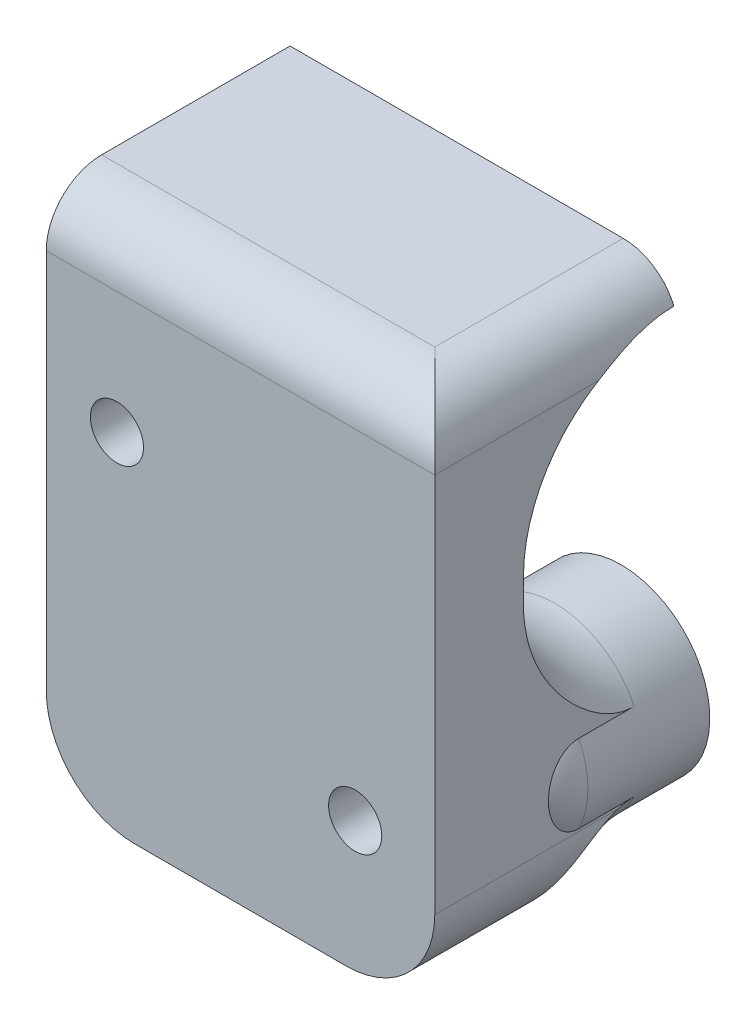
SolidWorks part; units mm, degrees
ref_plane "Front" through (0, 0, 0) normal (0, 0, 1) x (1, 0, 0)
ref_plane "Top" through (0, 0, 0) normal (0, 1, 0) x (1, 0, 0)
ref_plane "Right" through (0, 0, 0) normal (1, 0, 0) x (0, 0, -1)
sketch "Эскиз1" plane through (0, 0, 0) normal (0, 0, 1) x (1, 0, 0)
  line L0 (2.2009, 1.2487) -> (19.7294, 1.2487)
  line L1 (2.2009, 1.2487) -> (2.2009, 24.9297)
  line L2 (2.2009, 24.9297) -> (19.7294, 24.9297)
  line L3 (19.7294, 1.2487) -> (19.7294, 24.9297)
  circle A0 centre (16.1394, 7.1297) radius 1.2
  circle A1 centre (5.3909, 16.9297) radius 1.1977
  dimension "D1" = 3.19
  dimension "D2" = 17.5285
  dimension "D3" = 3.59
extrude "Бобышка-Вытянуть1" add sketch "Эскиз1" along normal blind 4
sketch "Эскиз2" plane through (0, 0, 0) normal (0, 0, -1) x (-1, 0, 0)
  line L0 (-2.2009, 24.9297) -> (-2.2009, 1.2487) construction
  line L1 (-19.7294, 24.9297) -> (-2.2009, 24.9297)
  line L2 (-19.7294, 24.9297) -> (-19.7294, 23.4297)
  line L3 (-19.7294, 23.4297) -> (-2.2009, 23.4297)
  line L4 (-2.2009, 24.9297) -> (-2.2009, 23.4297)
  dimension "D1" = 1.5
extrude "Бобышка-Вытянуть2" add sketch "Эскиз2" along normal blind 7
fillet "Скругление1" radius 4 2 edges at (2.2009, 1.2487, 2) (19.7294, 1.2487, 2)
sketch "Эскиз3" plane through (0, 0, 0) normal (0, 0, -1) x (-1, 0, 0)
  circle A0 centre (-16.1394, 7.1297) radius 1.1977
  circle A1 centre (-16.1394, 7.1297) radius 4
extrude "Бобышка-Вытянуть3" add sketch "Эскиз3" along normal blind 8
fillet "Скругление2" radius 5 1 edges at (12.1394, 7.1297, 0)
fillet "Скругление3" radius 7 1 edges at (10.9651, 23.4297, 0)
fillet "Скругление4" radius 2.5 1 edges at (20.1394, 7.1297, 0)
fillet "Скругление5" radius 2.5 2 edges at (10.9651, 24.9297, 4) (19.7294, 24.9297, -1.5)
sketch "Эскиз4" plane through (0, 0, 0) normal (0, 0, -1) x (-1, 0, 0)
  circle A0 centre (-5.3909, 16.9297) radius 7
extrude "Вырез-Вытянуть1" cut sketch "Эскиз4" along normal blind 10
